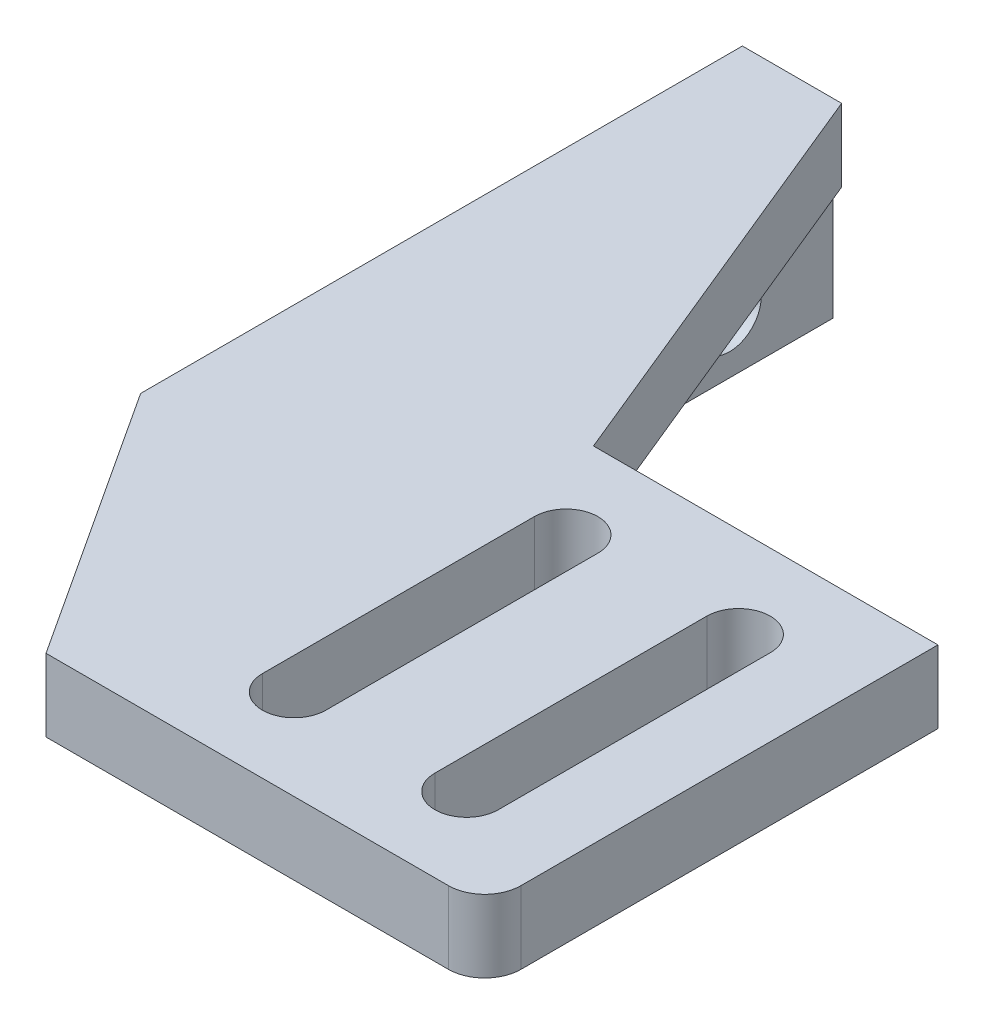
SolidWorks part; units mm, degrees
ref_plane "Piano frontale" through (0, 0, 0) normal (0, 0, 1) x (1, 0, 0)
ref_plane "Piano superiore" through (0, 0, 0) normal (0, 1, 0) x (1, 0, 0)
ref_plane "Piano destro" through (0, 0, 0) normal (1, 0, 0) x (0, 0, -1)
ref_plane "Piano1" through (0, 40, 0) normal (0, 1, 0) x (1, 0, 0)
sketch "Schizzo18" plane through (0, 40, 0) normal (0, 1, 0) x (1, 0, 0)
  line L0 (25, -16) -> (-9, -16)
  line L1 (25, -16) -> (25, 9)
  line L2 (25, 9) -> (6, 9)
  line L3 (-9, 32.2124) -> (-3.5247, 32.2124)
  line L4 (-9, -16) -> (-9, 32.2124)
  line L5 (-3.5247, 32.2124) -> (6, 9)
  line L6 (19, -16) -> (19, 9) construction
  line L7 (-9, -28.4145) -> (-9, 27.2974) construction
  line L8 (29.4558, 9) -> (-19.1855, 9) construction
  line L9 (25, -28.4145) -> (25, 27.2974) construction
  line L10 (29.4558, -16) -> (-19.1855, -16) construction
  line L11 (25, -11) -> (-9, -11) construction
  line L12 (25, 4) -> (-9, 4) construction
  line L13 (19, -11) -> (19, 4) construction
  line L14 (17.25, -11) -> (17.25, 4)
  line L15 (20.75, -11) -> (20.75, 4)
  line L16 (9.4906, -11) -> (9.4906, 4) construction
  line L17 (7.7406, -11) -> (7.7406, 4)
  line L18 (11.2406, -11) -> (11.2406, 4)
  arc A0 (17.25, -11) -> (20.75, -11) centre (19, -11) ccw
  arc A1 (20.75, 4) -> (17.25, 4) centre (19, 4) ccw
  arc A2 (7.7406, -11) -> (11.2406, -11) centre (9.4906, -11) ccw
  arc A3 (11.2406, 4) -> (7.7406, 4) centre (9.4906, 4) ccw
  point P22 (19, -3.5)
  point P29 (9.4906, -3.5)
  dimension "D6" = 15
  dimension "D1" = 6
  dimension "D2" = 25
  dimension "D3" = 34
  dimension "D4" = 5
  dimension "D5" = 15
extrude "Estrusione-Estrusione8" add sketch "Schizzo18" along normal blind 4 separate body
sketch "Schizzo19" plane through (0, 40, 0) normal (0, -1, 0) x (1, 0, 0)
  line L0 (-3.5247, -32.2124) -> (-9, -32.2124) construction
  line L1 (-9, 16) -> (-4, 16)
  line L2 (-9, 16) -> (-9, -32.2124)
  line L3 (-9, -32.2124) -> (-4, -32.2124)
  line L4 (-4, 16) -> (-4, -32.2124)
  dimension "D1" = 5
extrude "Estrusione-Estrusione9" add sketch "Schizzo19" along normal blind 6.5
sketch "Schizzo20" plane through (-9, 0, 0) normal (-1, 0, 0) x (0, 0, 1)
  line L0 (3.5, 44) -> (3.5, 33.5) construction
  line L1 (11, 44) -> (-4, 44) construction
  line L2 (16, 33.5) -> (-32.2124, 33.5) construction
  line L3 (-21.5, 44) -> (-21.5, 33.5) construction
  line L4 (-26.5, 44) -> (-26.5, 33.5) construction
  line L13 (-16.5, 44) -> (-16.5, 33.5) construction
  line L14 (-23.6103, 33.5) -> (25.3232, 33.5) construction
  line L15 (-23.6103, 36.5) -> (25.3232, 36.5) construction
  circle A0 centre (-26.5, 36.5) radius 1.75
  circle A1 centre (-16.5, 36.5) radius 1.75
  dimension "D1" = 25
  dimension "D2" = 5
  dimension "D3" = 5
  dimension "D4" = 3
extrude "Taglio-Estrusione9" cut sketch "Schizzo20" against normal blind 6
sketch "Schizzo21" plane through (-9, 0, 0) normal (-1, 0, 0) x (0, 0, 1)
  line L0 (16, 23.2712) -> (16, 48.2769) construction
  line L1 (1, 23.2712) -> (1, 48.2769) construction
  line L2 (16, 44) -> (16, 40.1473)
  dimension "D1" = 15
sketch "Schizzo24" plane through (0, 44, 0) normal (0, 1, 0) x (1, 0, 0)
  line L0 (-9, -16) -> (25, -16) construction
  line L2 (0.8051, -16) -> (-9, -0.979)
  line L3 (-9, 32.2124) -> (-9, -16) construction
  line L4 (-9, -0.979) -> (-9, -16)
  line L5 (-9, -16) -> (0.8051, -16)
extrude "Taglio-Estrusione13" cut sketch "Schizzo24" against normal blind 21
ref_plane "Piano2" through (0, 0, 0.979) normal (0, 0, 1) x (1, 0, 0)
sketch "Schizzo26" plane through (0, 0, 0.979) normal (0, 0, 1) x (1, 0, 0)
  line L0 (-9, 23.2712) -> (-9, 48.2769) construction
  line L1 (-4, 33.5) -> (-9, 33.5)
  line L2 (-4, 33.5) -> (-4, 40)
  line L3 (-4, 40) -> (-9, 40)
  line L4 (-9, 33.5) -> (-9, 40)
  line L5 (55, 40) -> (-55, 40) construction
extrude "Taglio-Estrusione15" cut sketch "Schizzo26" along normal blind 21
fillet "Raccordo1" radius 4 1 edges at (-6.5, 33.5, 0.979) type face fillet first side face at (-6.5, 36.75, 0.979) second side face at (-6.5, 33.5, -15.6167)
fillet "Raccordo2" radius 2 1 edges at (25, 42, 16) type face fillet first side face at (9.8782, 42, 16) second side face at (25, 42, 3.5)
